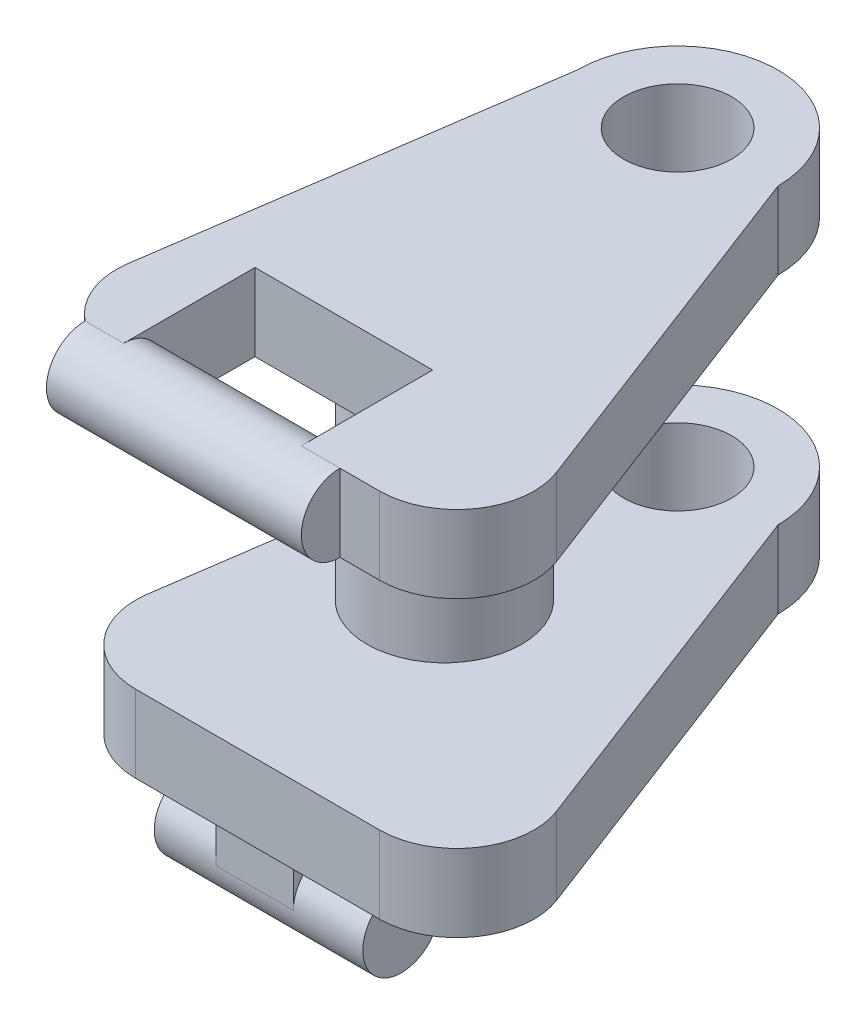
SolidWorks part; units mm, degrees
material "Alloy Steel (SS)"
ref_plane "Front Plane" through (0, 0, 0) normal (0, 0, 1) x (1, 0, 0)
ref_plane "Top Plane" through (0, 0, 0) normal (0, 1, 0) x (1, 0, 0)
ref_plane "Right Plane" through (0, 0, 0) normal (1, 0, 0) x (0, 0, -1)
sketch "Sketch1" plane through (0, 0, 0) normal (0, 1, 0) x (1, 0, 0)
  line L1 (3.2476, 60) -> (-5.4629, 0)
  line L2 (-5.4629, 0) -> (52.204, 0)
  line L5 (29.2476, 60) -> (52.204, 0)
  circle A0 centre (16.2476, 60) radius 7
  circle A1 centre (16.2476, 60) radius 13
extrude "Boss-Extrude2" add sketch "Sketch1" along normal blind 10 contours A1 L1 L2 L5 | A1 A0 region at (20.7328, 0, -22.8719) region at (16.2476, 0, -72.6323)
sketch "Sketch2" plane through (0, 0, 0) normal (0, -1, 0) x (1, 0, 0)
  circle A0 centre (16.0525, -30) radius 10
extrude "Boss-Extrude3" add sketch "Sketch2" along normal blind 28
sketch "Sketch3" plane through (0, -28, 0) normal (0, -1, 0) x (1, 0, 0)
  line L0 (3.2476, -60) -> (-5.4629, 0)
  line L1 (-5.4629, 0) -> (52.204, 0)
  line L2 (52.204, 0) -> (29.2476, -60)
  circle A0 centre (16.2476, -60) radius 7
  circle A1 centre (16.2476, -60) radius 13
  circle M1 centre (16.0525, -30) radius 10
extrude "Boss-Extrude4" add sketch "Sketch3" along normal blind 10 separate body contours A1 L2 L1 L0 M1 | A1 A0 region at (-0.2841, -28, -29.8804) region at (16.2476, -28, -47.3677)
sketch "Sketch4" plane through (0, -28, 0) normal (0, -1, 0) x (1, 0, 0)
  circle A0 centre (16.0525, -30) radius 10
extrude "Boss-Extrude5" add sketch "Sketch4" along normal blind 10
fillet "Fillet1" radius 10 2 edges at (52.204, -33, 0) (-5.4629, -33, 0)
sketch "Sketch5" plane through (0, 0, 0) normal (0, 0, 1) x (1, 0, 0)
  line L0 (-5.4629, 5) -> (4.5371, 5)
  line L1 (-5.4629, 10) -> (-5.4629, 0) construction
  line L2 (4.5371, 10) -> (4.5371, 0)
  line L3 (-5.4629, 10) -> (52.204, 10) construction
  line L4 (-5.4629, 0) -> (52.204, 0) construction
  line L5 (4.5371, 0) -> (27.5371, 0)
  line L6 (27.5371, 0) -> (27.5371, 10)
  line L7 (27.5371, 10) -> (4.5371, 10)
  line M3 (-5.4629, 0) -> (52.204, 0)
  line M5 (52.204, 10) -> (-5.4629, 10)
extrude "Cut-Extrude1" cut sketch "Sketch5" against normal blind 17 contours L6 L2 M3 M5 region at (16.0371, 5, 0)
sketch "Sketch6" plane through (27.5371, 0, 0) normal (-1, 0, 0) x (0, 0, 1)
  line L0 (0, 0) -> (0, 10) construction
  circle A0 centre (0, 5) radius 5
extrude "Boss-Extrude6" add sketch "Sketch6" along normal blind 28 and the other way blind 5
fillet "Fillet2" radius 10 2 edges at (52.204, 5, 0) (-5.4629, 5, 0)
sketch "Sketch7" plane through (0, -38, 0) normal (0, -1, 0) x (-1, 0, 0)
  line L0 (-16.0936, 0) -> (-16.0936, 10.3992)
  line L1 (-6.0936, 0) -> (-37.671, 0) construction
  line L2 (-6.0936, 0) -> (-16.0936, 0)
  line L3 (-11.0936, 15.3992) -> (-21.0936, 15.3992)
  line L4 (-11.0936, 15.3992) -> (-11.0936, 5.3992)
  line L5 (-11.0936, 5.3992) -> (-21.0936, 5.3992)
  line L6 (-21.0936, 15.3992) -> (-21.0936, 5.3992)
  line L7 (-11.0936, 15.3992) -> (-21.0936, 5.3992) construction
  line L8 (-11.0936, 5.3992) -> (-21.0936, 15.3992) construction
  arc A0 (-6.0936, 0) -> (3.8026, 11.4367) centre (-6.0936, 10) ccw construction
extrude "Boss-Extrude7" add sketch "Sketch7" along normal blind 10 contours L3 L6 L5 L4 region at (11.2351, -38, -10.3992)
sketch "Sketch8" plane through (21.0936, 0, 0) normal (1, 0, 0) x (0, 0, -1)
  line L0 (15.3992, -48) -> (5.3992, -48) construction
  circle A0 centre (10.3992, -48) radius 5
extrude "Boss-Extrude8" add sketch "Sketch8" along normal blind 9 and the other way blind 18
